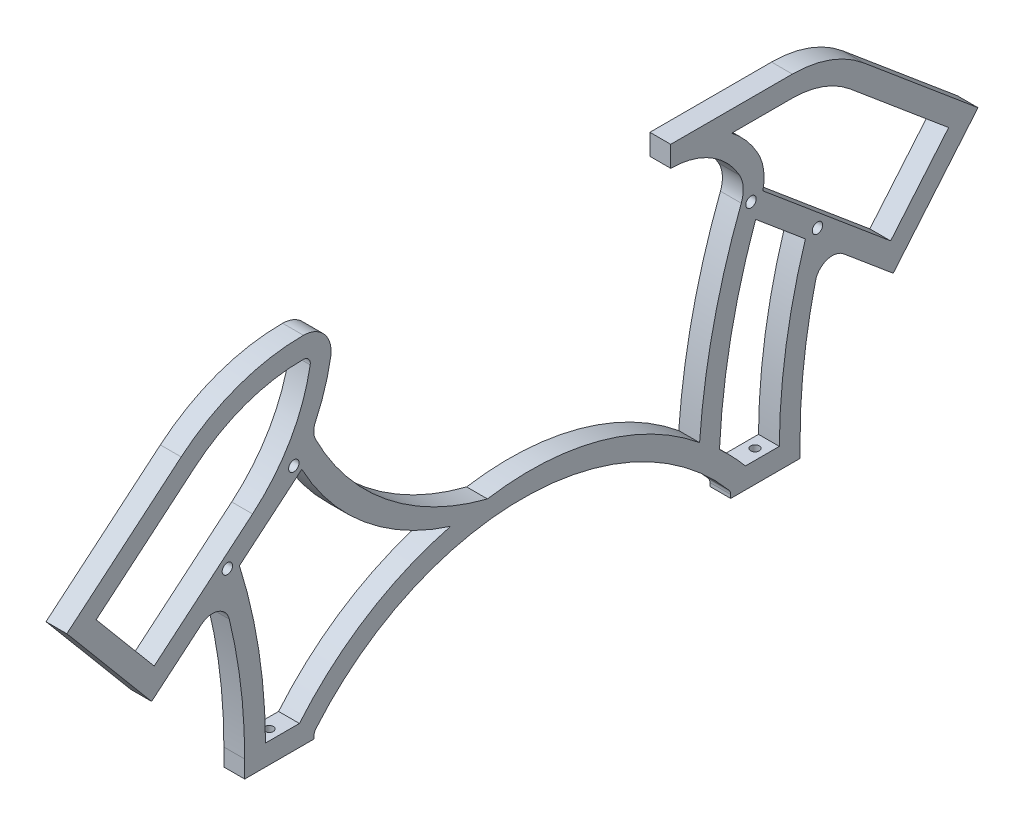
SolidWorks part; units mm, degrees
material "1060 Alloy"
ref_plane "Front Plane" through (0, 0, 0) normal (0, 0, 1) x (1, 0, 0)
ref_plane "Top Plane" through (0, 0, 0) normal (0, 1, 0) x (1, 0, 0)
ref_plane "Right Plane" through (0, 0, 0) normal (1, 0, 0) x (0, 0, -1)
sketch "Sketch1" plane through (0, 0, 0) normal (1, 0, 0) x (0, 0, -1)
  line L0 (0, 0) -> (0, 5)
  line L1 (-50.4789, 62.5279) -> (-24.1246, 31.1201) construction
  line L2 (-50.4789, 62.5279) -> (10.8047, 113.9509) construction
  line L3 (-24.1246, 31.1201) -> (37.1589, 82.5431) construction
  line L4 (-47.0184, 61.5154) -> (-26.4492, 37.0019) construction
  line L5 (10.8047, 113.9509) -> (37.1589, 82.5431) construction
  line L6 (20, 1) -> (20, 0)
  line L7 (0, 0) -> (20, 0)
  line L8 (-26.4492, 37.0019) -> (4.1925, 62.7135) construction
  line L9 (-16.3767, 87.2269) -> (-47.0184, 61.5154) construction
  line L10 (161.5267, 53.9982) -> (147.1775, 66.0387)
  line L11 (-18.305, 89.525) -> (-51.2449, 61.8851)
  line L12 (16.4447, 69.078) -> (-1.5267, 53.9982)
  line L13 (154.0031, 6) -> (144.2478, 6)
  line L14 (210.4789, 62.5279) -> (184.1246, 31.1201) construction
  line L15 (210.4789, 62.5279) -> (149.1953, 113.9509) construction
  line L16 (184.1246, 31.1201) -> (122.8411, 82.5431) construction
  line L17 (149.1953, 113.9509) -> (122.8411, 82.5431) construction
  line L18 (186.4492, 37.0019) -> (207.0184, 61.5154) construction
  line L19 (207.0184, 61.5154) -> (176.3767, 87.2269) construction
  line L20 (155.8075, 62.7135) -> (186.4492, 37.0019) construction
  line L21 (196.7338, 49.2587) -> (136.9824, 99.3961) construction
  line L22 (-36.7338, 49.2587) -> (23.0176, 99.3961) construction
  line L23 (15.7522, 6) -> (5.9969, 6)
  line L24 (172.518, 44.7754) -> (186.819, 32.7755)
  line L25 (186.819, 32.7755) -> (211.2449, 61.8851)
  line L26 (211.2449, 61.8851) -> (178.305, 89.525)
  line L27 (-51.2449, 61.8851) -> (-26.819, 32.7755)
  line L28 (160, 0) -> (160, 5)
  line L29 (-26.819, 32.7755) -> (-12.518, 44.7754)
  line L30 (-26.819, 32.7755) -> (6.1209, 60.4153) construction
  line L31 (149.2836, 72.1038) -> (186.0795, 41.2284)
  line L32 (186.0795, 41.2284) -> (202.792, 61.1456)
  line L33 (202.792, 61.1456) -> (174.4483, 84.9287)
  line L34 (109.9256, 30) -> (27.8477, 30) construction
  line L35 (109.9256, 36) -> (27.8477, 36) construction
  line L36 (145.0961, 75.6176) -> (165.3963, 58.5837) construction
  line L37 (-14.4483, 84.9287) -> (-42.792, 61.1456)
  line L38 (-42.792, 61.1456) -> (-26.0795, 41.2284)
  line L39 (-26.0795, 41.2284) -> (2.2642, 65.0116)
  line L40 (153.7344, 60.5368) -> (186.819, 32.7755) construction
  line L41 (145.0961, 75.6176) -> (162.13, 95.9178) construction
  line L42 (165.3963, 58.5837) -> (182.4301, 78.8839) construction
  line L43 (160, 0) -> (140, 0)
  line L44 (162.13, 95.9178) -> (182.4301, 78.8839) construction
  line L45 (157.7677, 97) -> (122.7225, 97)
  line L46 (122.7225, 97) -> (122.7225, 91)
  line L47 (157.7677, 91) -> (140.2944, 91)
  line L48 (157.8841, 64.8872) -> (186.0795, 41.2284) construction
  line L49 (122.7225, 91) -> (127.9357, 91) construction
  line L56 (140, 1) -> (140, 0)
  line L63 (174.6584, 98) -> (-14.1241, 98) construction
  circle A0 centre (-5, 55) radius 1.5
  circle A1 centre (165, 55) radius 1.5
  circle A2 centre (14.1511, 71.0697) radius 1.5
  circle A3 centre (145.8489, 71.0697) radius 1.5
  circle A4 centre (165, 55) radius 3 construction
  circle A5 centre (145.8489, 71.0697) radius 3 construction
  circle A6 centre (-5, 55) radius 3 construction
  circle A7 centre (14.1511, 71.0697) radius 3 construction
  arc A8 (178.305, 89.525) -> (157.7677, 97) centre (157.7677, 65.0495) ccw
  arc A9 (147.1775, 66.0387) -> (136.7721, 13.8377) centre (317.25, 5) ccw
  arc A10 (143.0497, 72.1487) -> (131.039, 18.4222) centre (317.25, 5) ccw
  arc A11 (20.3664, 78.9036) -> (24.7742, 92.9021) centre (-28.8526, 102.0951) ccw
  arc A12 (4.1925, 62.7135) -> (21.8174, 93.409) centre (-28.8526, 102.0951) ccw construction
  arc A13 (21.8174, 93.409) -> (16.9131, 99.2537) centre (16.8893, 94.2538) ccw construction
  arc A14 (16.9131, 99.2537) -> (-16.3767, 87.2269) centre (16.6685, 47.8452) ccw construction
  arc A15 (145.1274, 80.9224) -> (122.7225, 94) centre (122.7225, 68.2688) ccw construction
  arc A16 (149.2836, 72.1038) -> (147.7396, 82.3977) centre (135.0514, 75.2318) ccw
  arc A17 (147.7396, 82.3977) -> (140.2944, 91) centre (122.7225, 68.2688) ccw
  arc A18 (24.7742, 92.9021) -> (16.9273, 102.2537) centre (16.8893, 94.2538) ccw
  arc A19 (16.9273, 102.2537) -> (-18.305, 89.525) centre (16.6685, 47.8452) ccw
  arc A20 (165, 55) -> (157.0746, 9.8876) centre (317.25, 5) ccw construction
  arc A21 (143.0497, 72.1487) -> (142.5152, 79.4471) centre (135.0514, 75.2318) ccw
  arc A22 (145.8489, 71.0697) -> (133.9885, 17.5996) centre (317.25, 5) ccw construction
  arc A23 (6.1209, 60.4153) -> (24.7742, 92.9021) centre (-28.8526, 102.0951) ccw construction
  arc A24 (144.2478, 6) -> (136.7721, 13.8377) centre (80, -47.7963) ccw
  arc A25 (59.2881, 33.4) -> (16.4447, 69.078) centre (81.3836, 103.4959) cw
  arc A26 (20, 1) -> (20.4696, 2.2876) centre (22, 1) cw
  arc A27 (2.2642, 65.0116) -> (18.8605, 93.9159) centre (-28.8526, 102.0951) ccw
  arc A28 (18.8605, 93.9159) -> (16.8988, 96.2538) centre (16.8893, 94.2538) ccw
  arc A29 (16.8988, 96.2538) -> (-14.4483, 84.9287) centre (16.6685, 47.8452) ccw
  arc A30 (139.2609, 85.3778) -> (153.7344, 60.5368) centre (201.8446, 105.2049) ccw construction
  arc A31 (131.039, 18.4222) -> (69.9273, 34.9316) centre (82.1444, -41.2064) ccw
  arc A32 (160, 5) -> (164.4454, 42.1257) centre (317.25, 5) cw
  arc A33 (172.518, 44.7754) -> (164.4454, 42.1257) centre (169.3041, 40.9452) ccw
  arc A34 (0, 5) -> (-4.4454, 42.1257) centre (-157.25, 5) ccw
  arc A35 (-12.518, 44.7754) -> (-4.4454, 42.1257) centre (-9.3041, 40.9452) cw
  arc A36 (145.8489, 71.0697) -> (145.1274, 80.9224) centre (135.0514, 75.2318) ccw construction
  arc A37 (20.3664, 78.9036) -> (20.3696, 74.6344) centre (24.8894, 76.7724) ccw
  arc A38 (174.4483, 84.9287) -> (157.7677, 91) centre (157.7677, 65.0495) ccw
  arc A39 (161.5267, 53.9982) -> (154.0031, 6) centre (317.25, 5) ccw
  arc A40 (-1.5267, 53.9982) -> (5.9969, 6) centre (-157.25, 5) cw
  arc A41 (59.2881, 33.4) -> (15.7522, 6) centre (80, -47.7963) ccw
  arc A42 (144.0205, 95.2626) -> (139.2609, 85.3778) centre (146.8873, 87.7939) ccw construction
  arc A43 (142.5152, 79.4471) -> (122.7225, 91) centre (122.7225, 68.2688) ccw
  arc A44 (140, 1) -> (139.5304, 2.2876) centre (138, 1) ccw
  arc A45 (139.5304, 2.2876) -> (20.4696, 2.2876) centre (80, -47.7963) ccw
  arc A46 (144.9807, 87.1899) -> (157.8841, 64.8872) centre (201.8446, 105.2049) ccw construction
  arc A47 (174.4483, 84.9287) -> (146.1706, 89.6611) centre (156.2924, 63.2914) ccw construction
  arc A48 (178.305, 89.525) -> (144.0205, 95.2626) centre (156.2924, 63.2914) ccw construction
  arc A49 (146.1706, 89.6611) -> (144.9807, 87.1899) centre (146.8873, 87.7939) ccw construction
  arc A50 (69.9273, 34.9316) -> (20.3696, 74.6344) centre (88.5641, 108.9752) cw
  arc A51 (142.1208, 86.2838) -> (155.8075, 62.7135) centre (201.8446, 105.2049) ccw construction
  arc A52 (145.0956, 92.4618) -> (142.1208, 86.2838) centre (146.8873, 87.7939) ccw construction
  arc A53 (176.3767, 87.2269) -> (145.0956, 92.4618) centre (156.2924, 63.2914) ccw construction
  dimension "D1" = 3
  dimension "D8" = 5
  dimension "D11" = 55
  dimension "D12" = 5
  dimension "D14" = 25
  dimension "D16" = 2
  dimension "D17" = 6
  dimension "D21" = 40
  dimension "D22" = 35
  dimension "D23" = 80
  dimension "D24" = 3
  dimension "D18" = 6
  dimension "D29" = 55
  dimension "D25" = 6
  dimension "D28" = 6
  dimension "D36" = 5
  dimension "D37" = 6
  dimension "D38" = 3
  dimension "D39" = 8
  dimension "D40" = 10
  dimension "D45" = 97
  dimension "D46" = 6
  dimension "D47" = 6
  dimension "D48" = 6
  dimension "D49" = 30
  dimension "D52" = 26.5
  dimension "D53" = 3
  dimension "D54" = 6
  dimension "D56" = 2
  dimension "D30" = 3
  dimension "D4" = 25
  dimension "D6" = 28
  dimension "D7" = 5
  dimension "D9" = 20
  dimension "D10" = 120
  dimension "D13" = 1
  dimension "D15" = 40
  dimension "D19" = 40
  dimension "D20" = 30
  dimension "D26" = 3
  dimension "D27" = 2
  dimension "D31" = 3
  dimension "D32" = 98
  dimension "D33" = 3
  dimension "D34" = 6
  dimension "D35" = 3
  dimension "D41" = 3
  dimension "D42" = 3
  dimension "D43" = 6
  dimension "D44" = 6
  dimension "D50" = 3.5
  dimension "D51" = 26.5
extrude "Boss-Extrude1" add sketch "Sketch1" along normal blind 6
hole_wizard "Tap Drill for M3 Tap1" positions "Sketch3" profile "Sketch2" hole size "M3" standard "ISO"
sketch "Sketch3" plane through (0, 0, 0) normal (0, -1, 0) x (-1, 0, 0)
  line L0 (-6, 20) -> (0, 20) construction
  line L1 (0, 0) -> (0, 20) construction
  line L2 (-6, 140) -> (0, 140) construction
  point P0 (-3, 10)
  point P2 (-3, 150)
  dimension "D1" = 10
  dimension "D2" = 3
  dimension "D3" = 10
sketch "Sketch2" plane through (3, 0, -10) normal (1, 0, 0) x (0, 0, -1)
  line L0 (0, 0) -> (0, 10.7511)
  line L1 (0, 10.7511) -> (1.25, 10)
  line L2 (1.25, 10) -> (1.25, 0)
  line L5 (1.25, 0) -> (0, 0)
  line L10 (0, 10.7511) -> (-1.25, 10) construction
  line L11 (0, -6.35) -> (0, 107.95) construction
  dimension "Hole Dia." = 2.5
  dimension "Hole Depth" = 10
  dimension "Drill Angle" = 118
equation "\"ˇ35\"=76.24"
